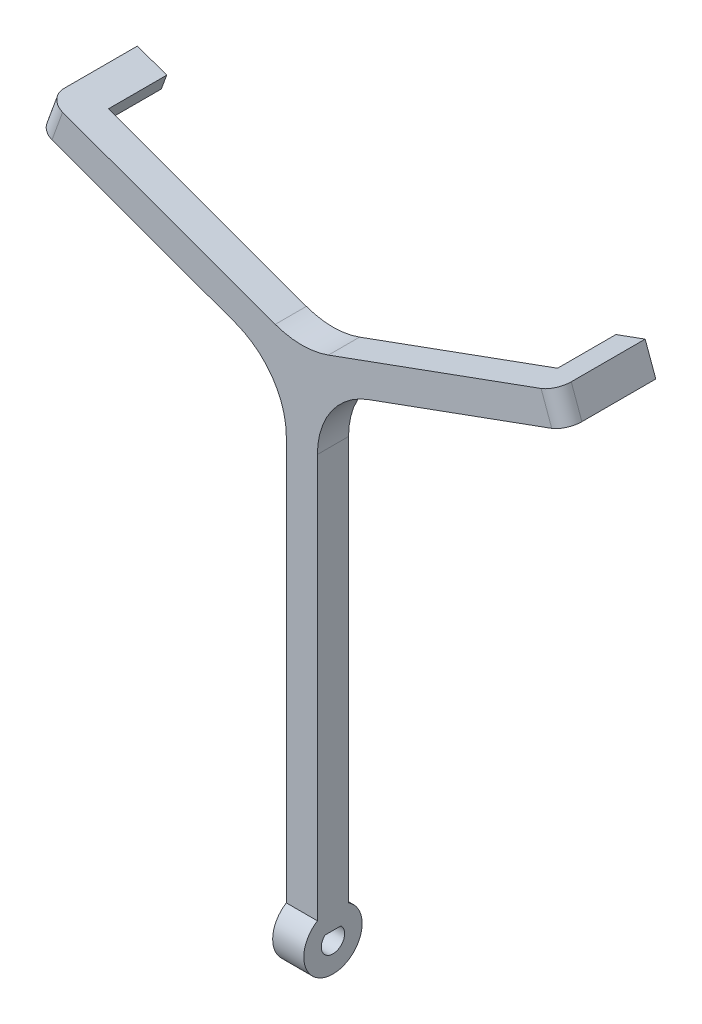
SolidWorks part; units mm, degrees
material "PLA"
ref_plane "Plan de face" through (0, 0, 0) normal (0, 0, 1) x (1, 0, 0)
ref_plane "Plan de dessus" through (0, 0, 0) normal (0, 1, 0) x (1, 0, 0)
ref_plane "Plan de droite" through (0, 0, 0) normal (1, 0, 0) x (0, 0, -1)
sketch "Esquisse1" plane through (0, 0, 0) normal (0, 0, 1) x (1, 0, 0)
  line L1 (0, 0) -> (136, 0) construction
  line L2 (0, 0) -> (0, 155) construction
  line L3 (0, 155) -> (136, 155) construction
  line L4 (136, 0) -> (136, 155) construction
  line L16 (64, 0) -> (64, 124.1884)
  line L17 (64, 124.1884) -> (0, 147.4825)
  line L18 (0, 147.4825) -> (2.7362, 155)
  line L19 (2.7362, 155) -> (68, 131.2459)
  line L20 (68, 131.2459) -> (133.2638, 155)
  line L21 (133.2638, 155) -> (136, 147.4825)
  line L22 (136, 147.4825) -> (72, 124.1884)
  line L23 (72, 124.1884) -> (72, 0)
  line L24 (72, 0) -> (64, 0)
  point P19 (68, 0)
  dimension "D1" = 136
  dimension "D2" = 155
  dimension "D3" = 8
  dimension "D4" = 68
  dimension "D5" = 110
  dimension "D6" = 110
  dimension "D7" = 140
  dimension "D8" = 8
  dimension "D9" = 8
  dimension "D10" = 68
extrude "Boss.-Extru.1" add sketch "Esquisse1" along normal blind 8
sketch "Esquisse2" plane through (0, 0, 0) normal (0, 0, -1) x (-1, 0, 0)
  line L0 (-72, 124.1884) -> (-136, 147.4825) construction
  line L1 (-136, 147.4825) -> (-133.2638, 155) construction
  line L2 (-133.2638, 155) -> (-68, 131.2459) construction
  line L3 (-132.2412, 146.1144) -> (-136, 147.4825)
  line L4 (-136, 147.4825) -> (-133.2638, 155)
  line L5 (-133.2638, 155) -> (-125.7463, 152.2638)
  line L6 (-127.1144, 148.5051) -> (-125.7463, 152.2638)
  line L7 (0, 147.4825) -> (-64, 124.1884) construction
  line L8 (-68, 131.2459) -> (-2.7362, 155) construction
  line L9 (-2.7362, 155) -> (0, 147.4825) construction
  line L10 (0, 147.4825) -> (-3.7588, 146.1144)
  line L11 (-10.2537, 152.2638) -> (-2.7362, 155)
  line L12 (-2.7362, 155) -> (0, 147.4825)
  line L13 (-10.2537, 152.2638) -> (-8.8856, 148.5051)
  line L14 (-132.2412, 146.1144) -> (-127.1144, 148.5051)
  line L15 (-8.8856, 148.5051) -> (-3.7588, 146.1144)
  dimension "D2" = 8
  dimension "D1" = 8
  dimension "D3" = 4
  dimension "D4" = 4
  dimension "D5" = 4
  dimension "D6" = 4
extrude "Boss.-Extru.2" add sketch "Esquisse2" along normal blind 15
fillet "Congé1" radius 20 3 edges at (72, 124.1884, 4) (64, 124.1884, 4) (68, 131.2459, 4)
fillet "Congé2" radius 4 2 edges at (134.6319, 151.2412, 8) (1.3681, 151.2412, 8)
sketch "Esquisse3" plane through (64, 0, 0) normal (-1, 0, 0) x (0, 0, 1)
  line L0 (4, 0) -> (4, 33.6289) construction
  line L1 (8, 0) -> (0, 0) construction
  circle A0 centre (4, 0) radius 7.5
  dimension "D1" = 15
extrude "Boss.-Extru.3" add sketch "Esquisse3" against normal up to surface (8 mm away) up to face at (72, 55.0921, 4)
sketch "Esquisse4" plane through (64, 0, 0) normal (-1, 0, 0) x (0, 0, 1)
  line L7 (4, 0) -> (4, 7.4852) construction
  line L11 (1.9604, 2.2) -> (6.0396, 2.2)
  line L12 (0.3981, -3) -> (8.2082, -3) construction
  arc A1 (1.9604, 2.2) -> (6.0396, 2.2) centre (4, 0) ccw
  point P10 (4, 6)
  point P11 (4, 6)
  dimension "D1" = 6
  dimension "D2" = 5.2
extrude "Enlèv. mat.-Extru.1" cut sketch "Esquisse4" against normal through all
equation "\"long_tot\"=155"
equation "\"espac_sub_arms\"= 120"
equation "\"épaiss_cadre\"=8"
equation "\"long_protub\"= 15"
equation "\"rayon_conge\"= 3"
equation "\"diam_axe\"= 5"
equation "\"D1@Esquisse1\"=\"espac_sub_arms\"+\"épaiss_cadre\"*2"
equation "\"D2@Esquisse1\"=\"long_tot\""
equation "\"D3@Esquisse1\"=\"épaiss_cadre\""
equation "\"D4@Esquisse1\"=\"D1@Esquisse1\"/2"
equation "\"D6@Esquisse1\"=\"D5@Esquisse1\""
equation "\"D8@Esquisse1\"=\"épaiss_cadre\""
equation "\"D9@Esquisse1\"=\"épaiss_cadre\""
equation "\"D10@Esquisse1\"=\"D4@Esquisse1\""
equation "\"D1@Boss.-Extru.1\"=\"épaiss_cadre\""
equation "\"D2@Esquisse2\"=\"épaiss_cadre\""
equation "\"D1@Boss.-Extru.2\"=\"long_protub\""
equation "\"D1@Esquisse2\"=\"épaiss_cadre\""
equation "\"D3@Esquisse2\"=\"D1@Esquisse2\"/2"
equation "\"D4@Esquisse2\"=\"D1@Esquisse2\"/2"
equation "\"D5@Esquisse2\"=\"D2@Esquisse2\"/2"
equation "\"D6@Esquisse2\"=\"D2@Esquisse2\"/2"
